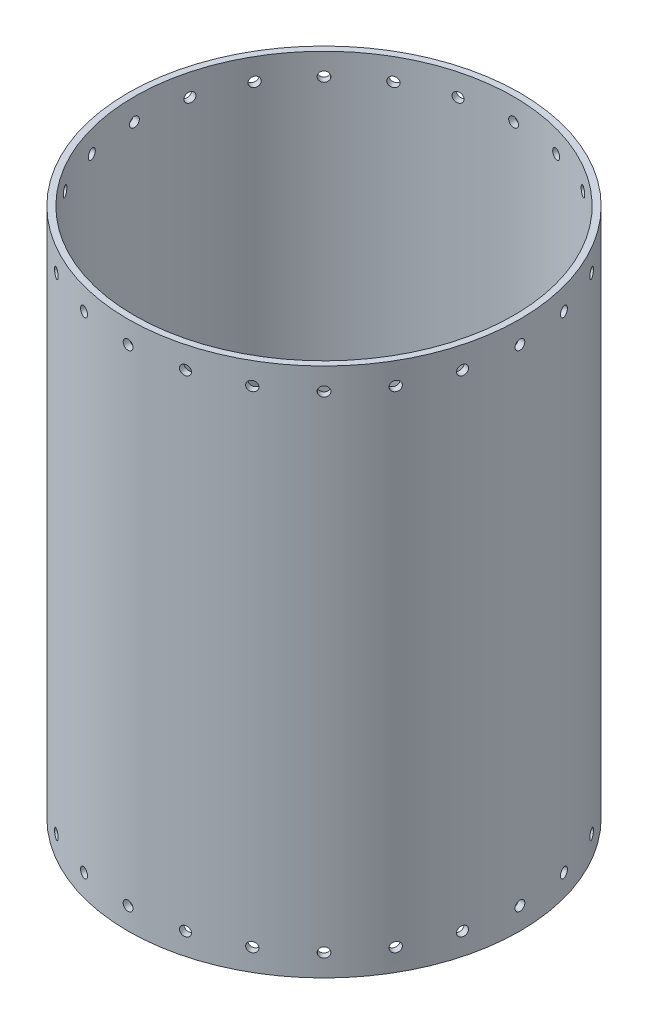
SolidWorks part; units mm, degrees
material "6061-T6 (SS)"
ref_plane "Front Plane" through (0, 0, 0) normal (0, 0, 1) x (1, 0, 0)
ref_plane "Top Plane" through (0, 0, 0) normal (0, 1, 0) x (1, 0, 0)
ref_plane "Right Plane" through (0, 0, 0) normal (1, 0, 0) x (0, 0, -1)
sketch "Sketch1" plane through (0, 0, 0) normal (0, 1, 0) x (1, 0, 0)
  circle A0 centre (0, 0) radius 98.425
  dimension "D1" = 196.85
extrude "Extrude-Thin1" add sketch "Sketch1" along normal blind 275.082 thin thin type one direction wall 3.302
ref_plane "Plane1" through (0, 263.652, 0) normal (0, 1, 0) x (1, 0, 0)
sketch "Sketch2" plane through (0, 263.652, 0) normal (0, 1, 0) x (1, 0, 0)
  line L0 (0, 0) -> (0, -116.6708) construction
  line L2 (0, -93.98) -> (2.54, -93.98)
  line L3 (0, -93.98) -> (0, -106.68)
  line L4 (0, -106.68) -> (2.54, -106.68)
  line L5 (2.54, -93.98) -> (2.54, -106.68)
  point P7 (-2.54, -93.98)
  dimension "D1" = 12.7
  dimension "D2" = 5.08
  dimension "D3" = 2.54
  dimension "D4" = 93.98
revolve "Cut-Revolve1" cut sketch "Sketch2" angle 360 about L0
sketch "Sketch3" plane through (0, 0, 0) normal (0, 0, 1) x (1, 0, 0)
  line L0 (0, 0) -> (0, 275.082) construction
  line L1 (98.425, 275.082) -> (-98.425, 275.082) construction
pattern_circular "CirPattern1" count 24 over 360 about axis through (0, 0, 0) along (0, 1, 0) of "Cut-Revolve1" reverse direction yes
ref_plane "Plane2" through (0, 137.541, 0) normal (0, 1, 0) x (1, 0, 0)
mirror "Mirror1" about plane through (0, 137.541, 0) normal (0, 1, 0) of "CirPattern1"
